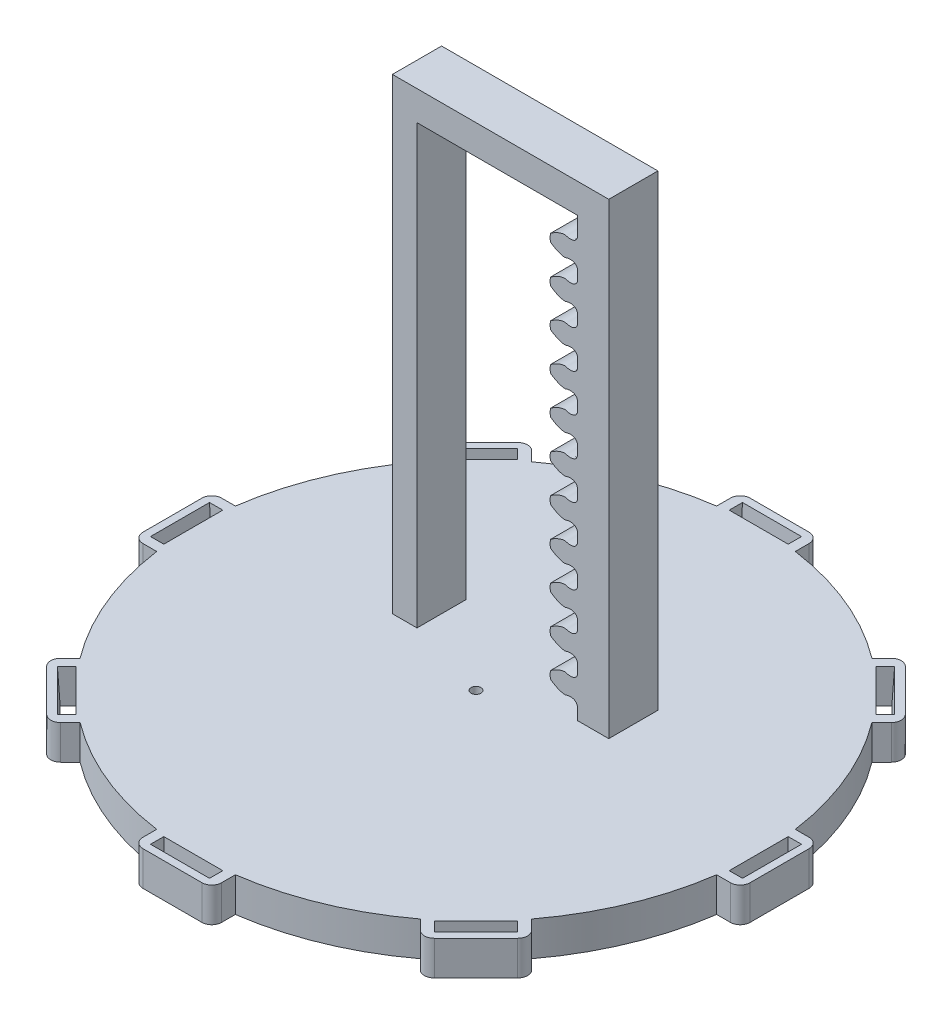
SolidWorks part; units mm, degrees
ref_plane "Front Plane" through (0, 0, 0) normal (0, 0, 1) x (1, 0, 0)
ref_plane "Top Plane" through (0, 0, 0) normal (0, 1, 0) x (1, 0, 0)
ref_plane "Right Plane" through (0, 0, 0) normal (1, 0, 0) x (0, 0, -1)
sketch "Sketch1" plane through (0, 0, 0) normal (0, 1, 0) x (1, 0, 0)
  line L0 (-8, 56.9408) -> (-8, 59.7408)
  line L1 (0, 57.5) -> (0, -57.5) construction
  line L2 (8, 56.9408) -> (8, 59.7408)
  line L3 (-6, 61.7408) -> (6, 61.7408)
  line L4 (39.4147, 47.8999) -> (47.8999, 39.4147)
  line L9 (34.6063, 45.9201) -> (36.5862, 47.8999)
  line L10 (45.9201, 34.6063) -> (47.8999, 36.5862)
  line L15 (61.7408, 6) -> (61.7408, -6)
  line L16 (56.9408, 8) -> (59.7408, 8)
  line L17 (56.9408, -8) -> (59.7408, -8)
  line L22 (47.8999, -39.4147) -> (39.4147, -47.8999)
  line L23 (45.9201, -34.6063) -> (47.8999, -36.5862)
  line L24 (34.6063, -45.9201) -> (36.5862, -47.8999)
  line L29 (6, -61.7408) -> (-6, -61.7408)
  line L30 (8, -56.9408) -> (8, -59.7408)
  line L31 (-8, -56.9408) -> (-8, -59.7408)
  line L36 (-39.4147, -47.8999) -> (-47.8999, -39.4147)
  line L37 (-34.6063, -45.9201) -> (-36.5862, -47.8999)
  line L38 (-45.9201, -34.6063) -> (-47.8999, -36.5862)
  line L43 (-61.7408, -6) -> (-61.7408, 6)
  line L44 (-56.9408, -8) -> (-59.7408, -8)
  line L45 (-56.9408, 8) -> (-59.7408, 8)
  line L50 (-47.8999, 39.4147) -> (-39.4147, 47.8999)
  line L51 (-45.9201, 34.6063) -> (-47.8999, 36.5862)
  line L52 (-34.6063, 45.9201) -> (-36.5862, 47.8999)
  arc A0 (-8, 56.9408) -> (-34.6063, 45.9201) centre (0, 0) ccw
  arc A1 (6, 61.7408) -> (8, 59.7408) centre (6, 59.7408) cw
  arc A2 (-6, 61.7408) -> (-8, 59.7408) centre (-6, 59.7408) ccw
  arc A3 (39.4147, 47.8999) -> (36.5862, 47.8999) centre (38.0005, 46.4857) ccw
  arc A4 (47.8999, 39.4147) -> (47.8999, 36.5862) centre (46.4857, 38.0005) cw
  arc A5 (61.7408, 6) -> (59.7408, 8) centre (59.7408, 6) ccw
  arc A6 (61.7408, -6) -> (59.7408, -8) centre (59.7408, -6) cw
  arc A7 (47.8999, -39.4147) -> (47.8999, -36.5862) centre (46.4857, -38.0005) ccw
  arc A8 (39.4147, -47.8999) -> (36.5862, -47.8999) centre (38.0005, -46.4857) cw
  arc A9 (6, -61.7408) -> (8, -59.7408) centre (6, -59.7408) ccw
  arc A10 (-6, -61.7408) -> (-8, -59.7408) centre (-6, -59.7408) cw
  arc A11 (-39.4147, -47.8999) -> (-36.5862, -47.8999) centre (-38.0005, -46.4857) ccw
  arc A12 (-47.8999, -39.4147) -> (-47.8999, -36.5862) centre (-46.4857, -38.0005) cw
  arc A13 (-61.7408, -6) -> (-59.7408, -8) centre (-59.7408, -6) ccw
  arc A14 (-61.7408, 6) -> (-59.7408, 8) centre (-59.7408, 6) cw
  arc A15 (-47.8999, 39.4147) -> (-47.8999, 36.5862) centre (-46.4857, 38.0005) ccw
  arc A16 (-39.4147, 47.8999) -> (-36.5862, 47.8999) centre (-38.0005, 46.4857) cw
  arc A17 (-45.9201, 34.6063) -> (-56.9408, 8) centre (0, 0) ccw
  arc A18 (-56.9408, -8) -> (-45.9201, -34.6063) centre (0, 0) ccw
  arc A19 (34.6063, 45.9201) -> (8, 56.9408) centre (0, 0) ccw
  arc A20 (-34.6063, -45.9201) -> (-8, -56.9408) centre (0, 0) ccw
  arc A21 (8, -56.9408) -> (34.6063, -45.9201) centre (0, 0) ccw
  arc A22 (45.9201, -34.6063) -> (56.9408, -8) centre (0, 0) ccw
  arc A23 (56.9408, 8) -> (45.9201, 34.6063) centre (0, 0) ccw
  point P11 (8, 61.7408)
  point P14 (-8, 61.7408)
  point P17 (-8, 58.3408)
  point P98 (0, 0)
  dimension "D1" = 115
  dimension "D2" = 2
  dimension "D3" = 16
  dimension "D4" = 2.8
  dimension "D7" = 8
extrude "Boss-Extrude1" add sketch "Sketch1" along normal blind 7
sketch "Sketch2" plane through (0, 7, 0) normal (0, 1, 0) x (1, 0, 0)
  line L0 (-57.5, 0) -> (57.5, 0) construction
  line L1 (0, 0) -> (0, 10) construction
  line L7 (15.6, 5) -> (22, 5)
  line L14 (0, 10) -> (28.3122, 10) construction
  line L15 (0, 10) -> (-19.5, 10) construction
  line L17 (15.6, 5) -> (15.6, 15)
  line L18 (-22, 15) -> (-17, 15)
  line L19 (-22, 15) -> (-22, 5)
  line L20 (-22, 5) -> (-17, 5)
  line L21 (-17, 15) -> (-17, 5)
  line L22 (-22, 15) -> (-17, 5) construction
  line L23 (-22, 5) -> (-17, 15) construction
  line L24 (15.6, 15) -> (22, 15)
  line L25 (22, 5) -> (22, 15)
  line L26 (15.6, 5) -> (22, 15) construction
  line L27 (15.6, 15) -> (22, 5) construction
  circle A0 centre (0, 0) radius 57.5 construction
  point P8 (18.8, 10)
  dimension "D1" = 10
  dimension "D2" = 17
  dimension "D3" = 15.6
  dimension "D4" = 10
  dimension "D5" = 5
  dimension "D6" = 10
  dimension "D7" = 22
extrude "Boss-Extrude2" add sketch "Sketch2" along normal blind 95
sketch "Sketch15" plane through (0, 0, 0) normal (0, -1, 0) x (1, 0, 0)
  circle A0 centre (0, 0) radius 1
  dimension "D1" = 2
extrude "Cut-Extrude3" cut sketch "Sketch15" along direction (0, 1, 0) on the side against the normal up to surface (7 mm away) contours A0 up to face at (0, 7, 0)
sketch "Sketch16" plane through (0, 0, 0) normal (0, -1, 0) x (1, 0, 0)
  line L1 (-6, 59.8) -> (6, 59.8)
  line L2 (-6, 59.8) -> (-6, 57.5)
  line L3 (-6, 57.5) -> (6, 57.5)
  line L4 (6, 59.8) -> (6, 57.5)
  point P5 (0, 57.5)
  dimension "D1" = 2.3
  dimension "D2" = 12
  dimension "D3" = 57.5
sketch "Sketch17" plane through (0, 7, 0) normal (0, 1, 0) x (1, 0, 0)
  line L0 (-6, -57.5) -> (6, -57.5) construction
  line L1 (-6, -57.5) -> (6, -57.5)
  line L2 (-6, -57.5) -> (-6, -60.2)
  line L3 (-6, -60.2) -> (6, -60.2)
  line L4 (6, -60.2) -> (6, -57.5)
  dimension "D1" = 2.7
ref_axis "Axis1" through (0, 107.1, 0) along (0, -1, 0)
loft "Cut-Loft2" cut profiles "Sketch16", "Sketch17" connector at (6, 0, 59.8) connector at (6, 7, 60.2)
pattern_circular "CirPattern1" count 8 over 360 about axis through (0, 107.1, 0) along (0, -1, 0) of "Cut-Loft2"
sketch "Sketch19" plane through (0, 0, -15) normal (0, 0, -1) x (-1, 0, 0)
  line L0 (-15.6, 102) -> (-15.6, 7) construction
  line L1 (-22, 12.3067) -> (-15.6, 12.3067) construction
  line L2 (-22, 102) -> (-22, 7) construction
  line L3 (-22, 14.9882) -> (-12, 14.9882) construction
  line L4 (-22, 9.6251) -> (-15.6, 9.6251) construction
  line L5 (-22, 13.041) -> (-15.6, 13.041) construction
  line L6 (-22, 11.5722) -> (-15.6, 11.5722) construction
  line L7 (-16.3287, 12.3067) -> (-10.0944, 12.3067) construction
  line L8 (-15.6054, 9.6251) -> (-15.6054, 14.9882)
  line L9 (-22, 7) -> (-15.6, 7) construction
  arc A1 (-10.113, 11.5723) -> (-10.113, 13.041) centre (-24.5887, 12.3067) ccw
  spline S0 degree 3 poles (-10.113, 13.041) (-10.2539, 13.1479) (-10.4829, 13.3108) (-10.8032, 13.5139) (-11.0582, 13.6615) (-11.3032, 13.7904) (-11.5371, 13.9015) (-11.7588, 13.9961) (-11.9675, 14.0753) (-12.1623, 14.1404) (-12.3425, 14.1925) (-12.5072, 14.233) (-12.656, 14.2633) (-12.7881, 14.2845) (-12.9035, 14.299) (-13.0237, 14.3066) (-13.1765, 14.3233) (-13.3197, 14.2482) (-13.4591, 14.2128) (-13.5693, 14.1842) (-13.6781, 14.1609) (-13.7854, 14.1415) (-13.8912, 14.1264) (-13.9953, 14.1155) (-14.0979, 14.1088) (-14.199, 14.1063) (-14.2985, 14.1082) (-14.3964, 14.1144) (-14.4929, 14.1251) (-14.5878, 14.1404) (-14.6813, 14.1607) (-14.7733, 14.1861) (-14.8638, 14.2169) (-14.9525, 14.2537) (-15.0394, 14.2968) (-15.1241, 14.3467) (-15.2061, 14.404) (-15.2846, 14.4692) (-15.3587, 14.5426) (-15.4271, 14.6244) (-15.4884, 14.7145) (-15.5413, 14.812) (-15.5787, 14.9046) (-15.5981, 14.9642) (-15.6054, 14.9882) knots 0.011288 0.011288 0.011288 0.011288 0.05171 0.075523 0.097976 0.119068 0.138799 0.15717 0.17418 0.189829 0.204117 0.217044 0.228611 0.238817 0.247662 0.255146 0.266488 0.281932 0.290791 0.299458 0.307939 0.316243 0.324379 0.332357 0.340187 0.347883 0.35546 0.362932 0.370318 0.37764 0.384918 0.392178 0.399448 0.406756 0.414133 0.42161 0.429217 0.436977 0.444912 0.453029 0.461324 0.469778 0.478358 0.484106 0.484106 0.484106 0.484106
  spline S1 degree 3 poles (-15.6054, 9.6251) (-15.5981, 9.6491) (-15.5787, 9.7087) (-15.5413, 9.8013) (-15.4884, 9.8989) (-15.4271, 9.9889) (-15.3587, 10.0707) (-15.2846, 10.1441) (-15.2061, 10.2093) (-15.1241, 10.2666) (-15.0394, 10.3166) (-14.9525, 10.3596) (-14.8638, 10.3964) (-14.7733, 10.4273) (-14.6813, 10.4526) (-14.5878, 10.4729) (-14.4929, 10.4882) (-14.3964, 10.4989) (-14.2985, 10.5051) (-14.199, 10.507) (-14.0979, 10.5045) (-13.9953, 10.4978) (-13.8912, 10.4869) (-13.7854, 10.4718) (-13.6781, 10.4524) (-13.5693, 10.4291) (-13.4591, 10.4005) (-13.3197, 10.3651) (-13.1765, 10.29) (-13.0237, 10.3067) (-12.9035, 10.3143) (-12.7881, 10.3288) (-12.656, 10.35) (-12.5072, 10.3803) (-12.3425, 10.4208) (-12.1623, 10.473) (-11.9675, 10.538) (-11.7588, 10.6172) (-11.5371, 10.7118) (-11.3032, 10.8229) (-11.0582, 10.9518) (-10.8032, 11.0994) (-10.4829, 11.3025) (-10.2539, 11.4655) (-10.113, 11.5723) knots 0.515894 0.515894 0.515894 0.515894 0.521642 0.530222 0.538676 0.546971 0.555088 0.563023 0.570783 0.57839 0.585867 0.593244 0.600552 0.607822 0.615082 0.62236 0.629682 0.637068 0.64454 0.652117 0.659813 0.667643 0.675621 0.683757 0.692061 0.700542 0.709209 0.718068 0.733512 0.744854 0.752338 0.761183 0.771389 0.782956 0.795883 0.810171 0.82582 0.84283 0.861201 0.880932 0.902024 0.924477 0.94829 0.988712 0.988712 0.988712 0.988712
  dimension "D1" = 14.4943
  dimension "D2" = 5.487
  dimension "D3" = 0.0054
  dimension "D4" = 8.9887
  dimension "D5" = 2.6251
  dimension "D6" = 4.5722
  dimension "D7" = 4.5723
  dimension "D10" = 7.9882
extrude "Boss-Extrude3" add sketch "Sketch19" against normal up to surface (10 mm away) up to face at (18.8, 54.5, -5)
pattern_linear "LPattern1" count 11 spacing 7.7 along (0, 1, 0) of "Boss-Extrude3"
sketch "Sketch20" plane through (-17, 0, 0) normal (1, 0, 0) x (0, 0, -1)
  line L0 (15, 102) -> (15, 7) construction
  line L1 (5, 102) -> (15, 102)
  line L2 (5, 102) -> (5, 96)
  line L3 (5, 96) -> (15, 96)
  line L4 (15, 102) -> (15, 96)
  dimension "D1" = 6
extrude "Boss-Extrude4" add sketch "Sketch20" along normal up to next
equation "\"85.00.00mm\"=8500"
